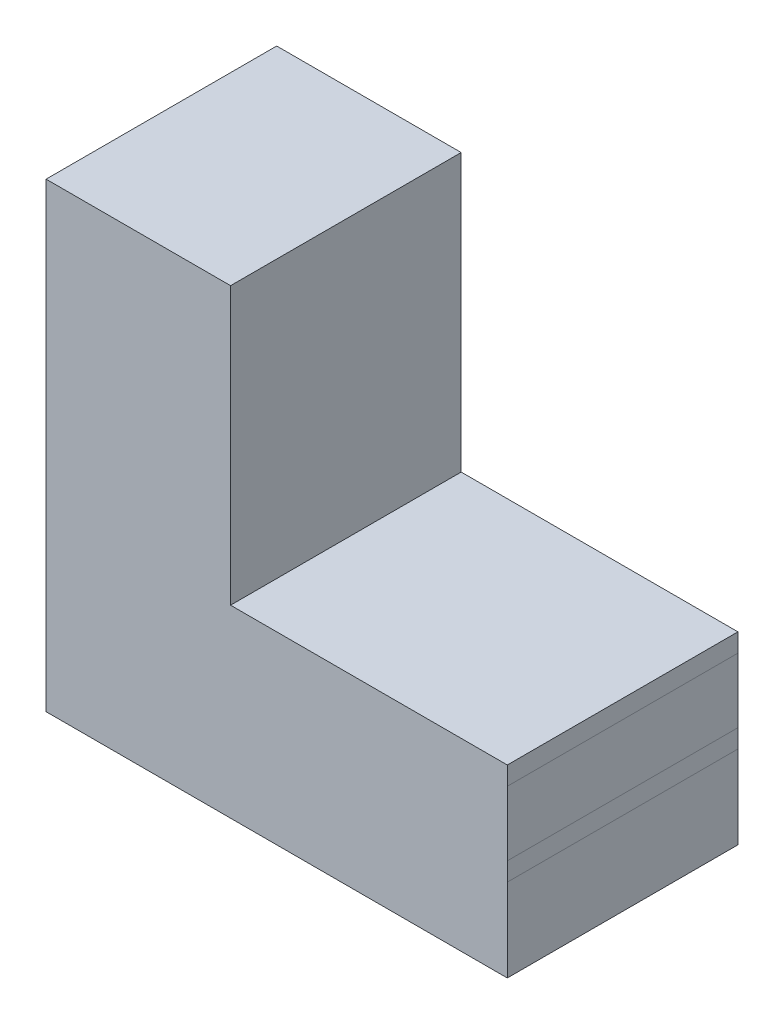
SolidWorks part; units mm, degrees
ref_plane "Front Plane" through (0, 0, 0) normal (0, 0, 1) x (1, 0, 0)
ref_plane "Top Plane" through (0, 0, 0) normal (0, 1, 0) x (1, 0, 0)
ref_plane "Right Plane" through (0, 0, 0) normal (1, 0, 0) x (0, 0, -1)
sketch "Sketch1" plane through (0, 0, 0) normal (0, 0, 1) x (1, 0, 0)
  line L0 (0, 0) -> (1000, 0)
  line L1 (1000, 0) -> (1000, 400)
  line L2 (1000, 400) -> (400, 400)
  line L3 (400, 400) -> (400, 1000)
  line L4 (400, 1000) -> (0, 1000)
  line L5 (0, 1000) -> (0, 0)
  dimension "D1" = 1000
  dimension "D2" = 600
  dimension "D3" = 400
  dimension "D4" = 1000
extrude "Boss-Extrude1" add sketch "Sketch1" along normal blind 500
sketch "Sketch3" plane through (1000, 0, 0) normal (1, 0, 0) x (0, 0, -1)
  line L0 (-500, 360) -> (0, 360)
  line L1 (-500, 0) -> (-500, 400) construction
  line L2 (0, 0) -> (0, 400) construction
  line L3 (-500, 400) -> (0, 400) construction
  line L4 (-500, 220) -> (0, 220)
  line L5 (-500, 180) -> (0, 180)
  line L6 (-500, 0) -> (0, 0) construction
  dimension "D1" = 40
  dimension "D2" = 40
  dimension "D3" = 180
split line "Split Line1"
